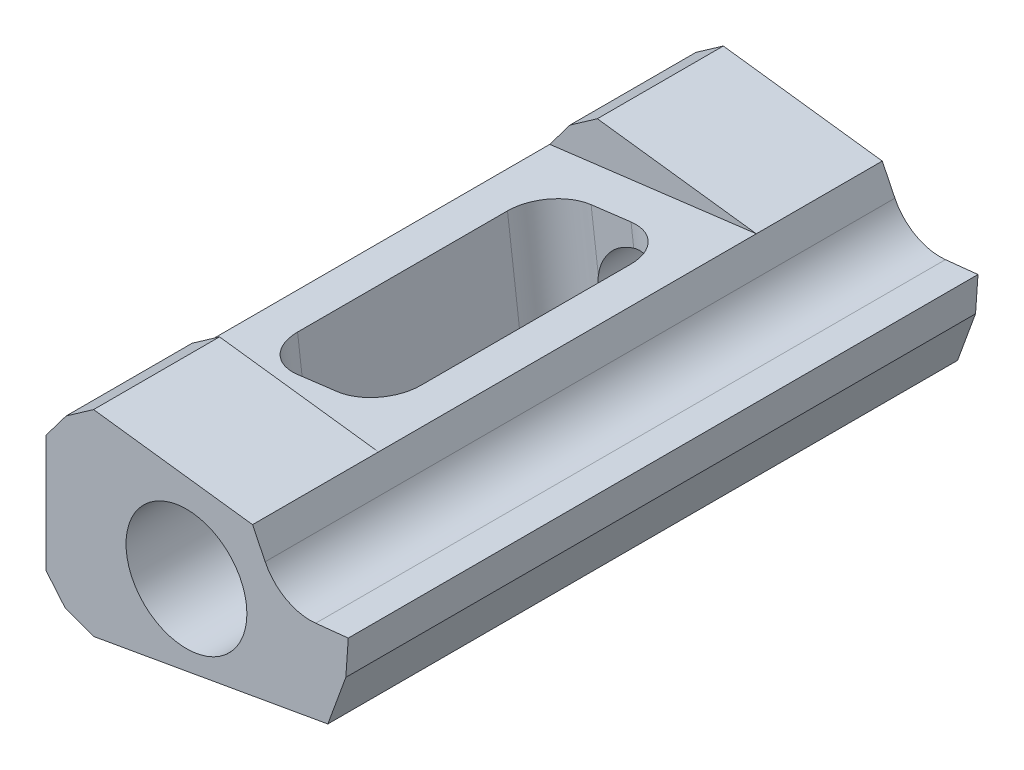
SolidWorks part; units mm, degrees
note: The reader was unsure of these and kept them because the rebuilt part matched: shared geometry of "Esboço7<3>", "Esboço7<4>".
material "AISI 4340 Aço, normalizado"
ref_plane "Plano frontal" through (0, 0, 0) normal (0, 0, 1) x (1, 0, 0)
ref_plane "Plano superior" through (0, 0, 0) normal (0, 1, 0) x (1, 0, 0)
ref_plane "Plano direito" through (0, 0, 0) normal (1, 0, 0) x (0, 0, -1)
other "Centro da massa"
sketch "Esboço1" plane through (0, 0, 0) normal (0, 0, 1) x (1, 0, 0)
  line L0 (0, 0) -> (23.1081, 0) construction
  line L1 (65, 0) -> (64.021, -14)
  line L2 (0, 0) -> (0, 38.7297) construction
  line L39 (27, 20) -> (-36.1134, 28)
  line L40 (-36.1134, 28) -> (-47, 20.3667)
  line L41 (-47, 20.3667) -> (-55, 9.7466)
  line L42 (-55, 9.7466) -> (-55, -36.7754)
  line L43 (-55, -36.7754) -> (-47.3284, -45.918)
  line L44 (-47.3284, -45.918) -> (-36.1134, -50)
  line L45 (-36.1134, -50) -> (56.8866, -33.6016)
  line L47 (56.8866, -33.6016) -> (64.021, -14)
  line L49 (65, 0) -> (52.0712, -1.3589)
  line L50 (32.0133, 9.7466) -> (27, 20)
  arc A0 (52.0712, -1.3589) -> (32.0133, 9.7466) centre (49.9806, 18.5316) cw
  dimension "D2" = 20
  dimension "D1" = 6
  dimension "D3" = 65
  dimension "D4" = 4
  dimension "D5" = 20
  dimension "D6" = 14
  dimension "D7" = 10
  dimension "D8" = 50
  dimension "D9" = 140
  dimension "D10" = 150
  dimension "D11" = 93
  dimension "D12" = 55
  dimension "D13" = 28
  dimension "D14" = 20
  dimension "D15" = 47
  dimension "D16" = 13
  dimension "D17" = 27
extrude "Ressalto-extrusão1" add sketch "Esboço1" along normal blind 250 contours L40 L41 L42 L43 L44 L45 L47 L1 L49 A0 L50 L39
scale "Escala1" scale about centroid uniform scaling yes scale factor 1.5
sketch "Esboço4" plane through (0, 0, -62.5) normal (0, 0, -1) x (-1, 0, 0)
  line L3 (80.808, -49.321) -> (69.3006, -63.0349) construction
  line L4 (69.3006, -63.0349) -> (52.478, -69.1578) construction
  line L5 (52.478, -69.1578) -> (-87.022, -44.5602) construction
  line L8 (80.808, -49.321) -> (69.3006, -63.0349)
  line L9 (69.3006, -63.0349) -> (52.478, -69.1578)
  line L10 (52.478, -69.1578) -> (-87.022, -44.5602)
  line L11 (52.478, 47.8422) -> (-42.192, 35.8422)
  line L12 (-42.192, 35.8422) -> (-49.712, 20.462)
  line L13 (-79.7988, 3.8039) -> (-99.192, 5.8422)
  line L14 (-99.192, 5.8422) -> (-97.7236, -15.1578)
  line L15 (-97.7236, -15.1578) -> (-87.022, -44.5602)
  line L16 (-87.022, -44.5602) -> (52.478, -69.1578)
  line L17 (52.478, -69.1578) -> (69.3006, -63.0349)
  line L18 (69.3006, -63.0349) -> (80.808, -49.321)
  line L19 (80.808, -49.321) -> (80.808, 20.462)
  line L20 (80.808, 20.462) -> (68.808, 36.3922)
  line L21 (68.808, 36.3922) -> (52.478, 47.8422)
  line L22 (52.478, 47.8422) -> (-42.192, 35.8422)
  line L31 (80.808, 20.462) -> (68.808, 36.3922)
  line L32 (68.808, 36.3922) -> (52.478, 47.8422)
  line L37 (-42.192, 35.8422) -> (80.808, 20.462)
  line L39 (-49.712, 20.462) -> (-42.192, 35.8422) construction
  line L40 (-87.022, -44.5602) -> (80.808, -49.321)
  arc A1 (-79.7988, 3.8039) -> (-49.712, 20.462) centre (-76.663, 33.6395) ccw
  point P3 (90.9399, 21.4695)
  dimension "D1" = 0
extrude "Corte-extrusão1" cut sketch "Esboço4" against normal offset from surface (225 mm away) 75 from offset 75 offset against normal yes
sketch "Esboço6" plane through (-3.7632, 30.0958, 0) normal (-0.1241, 0.9923, 0) x (0.9923, 0.1241, 0)
  line L0 (-46.1365, -12.5) -> (46.3131, -12.5) construction
  line L1 (-27.6447, -37.5) -> (-3.6869, -37.5)
  line L2 (-52.6447, -62.5) -> (-52.6447, -187.5)
  line L3 (-27.6447, -212.5) -> (-3.6869, -212.5)
  line L4 (21.3131, -62.5) -> (21.3131, -187.5)
  line L5 (46.3131, -237.5) -> (-46.1365, -237.5) construction
  line L6 (-77.6447, -237.5) -> (-77.6447, -12.5) construction
  line L7 (46.3131, -237.5) -> (46.3131, -12.5) construction
  arc A0 (-3.6869, -212.5) -> (21.3131, -187.5) centre (-3.6869, -187.5) ccw
  arc A1 (-52.6447, -187.5) -> (-27.6447, -212.5) centre (-27.6447, -187.5) ccw
  arc A2 (-3.6869, -37.5) -> (21.3131, -62.5) centre (-3.6869, -62.5) cw
  arc A3 (-27.6447, -37.5) -> (-52.6447, -62.5) centre (-27.6447, -62.5) ccw
  dimension "D5" = 25
  dimension "D1" = 25
  dimension "D2" = 25
  dimension "D3" = 25
  dimension "D4" = 25
extrude "Corte-extrusão3" cut sketch "Esboço6" against normal through all and the other way through all
sketch "Esboço7" plane through (0, 0, 312.5) normal (0, 0, 1) x (1, 0, 0)
  circle A0 centre (2.826, -11.7977) radius 36
  circle A1 centre (2.826, -11.7977) radius 30
  point P2 (-7.1795, -10.6794)
  point P3 (0, 0)
  point P4 (6.688, -14.5469)
  point P5 (2.826, -11.7977)
  dimension "D1" = 72
  dimension "D2" = 60
extrude "Corte-extrusão4" cut sketch "Esboço7" against normal blind 69 contours A0
extrude "Corte-extrusão5" cut sketch "Esboço7<3>" against normal through all contours A1
sketch "Esboço7<3>" plane through (0, 0, 312.5) normal (0, 0, 1) x (1, 0, 0) same geometry as "Esboço7"
extrude "Corte-extrusão6" cut sketch "Esboço7<4>" along normal blind 69 from surface at -375 starting at face at (32.826, -11.7977, -62.5)
sketch "Esboço7<4>" plane through (0, 0, 312.5) normal (0, 0, 1) x (1, 0, 0) same geometry as "Esboço7"
sketch "Esboço8" [suppressed] plane through (0, 0, 312.5) normal (0, 0, 1) x (1, 0, 0)
  circle A0 centre (0.7817, -11.1101) radius 101.6479
  circle A1 centre (0.7817, -11.1101) radius 36 construction
sketch "Esboço10" plane through (0, 0, 312.5) normal (0, 0, 1) x (1, 0, 0)
  line L11 (42.192, 35.8422) -> (-52.478, 47.8422)
  line L12 (-52.478, 47.8422) -> (-68.808, 36.3922)
  line L13 (-68.808, 36.3922) -> (-80.808, 20.462)
  line L14 (-80.808, 20.462) -> (-80.808, -49.321)
  line L15 (-80.808, -49.321) -> (-69.3006, -63.0349)
  line L16 (-69.3006, -63.0349) -> (-52.478, -69.1578)
  line L17 (-52.478, -69.1578) -> (87.022, -44.5602)
  line L18 (87.022, -44.5602) -> (97.7236, -15.1578)
  line L19 (97.7236, -15.1578) -> (99.192, 5.8422)
  line L20 (99.192, 5.8422) -> (79.7988, 3.8039)
  line L21 (49.712, 20.462) -> (42.192, 35.8422)
  line L22 (42.192, 35.8422) -> (-52.478, 47.8422)
  line L23 (-52.478, 47.8422) -> (-68.808, 36.3922)
  line L24 (-68.808, 36.3922) -> (-80.808, 20.462)
  line L25 (-80.808, 20.462) -> (-80.808, -49.321)
  line L26 (-80.808, -49.321) -> (-69.3006, -63.0349)
  line L27 (-69.3006, -63.0349) -> (-52.478, -69.1578)
  line L28 (-52.478, -69.1578) -> (87.022, -44.5602)
  line L29 (87.022, -44.5602) -> (97.7236, -15.1578)
  line L30 (97.7236, -15.1578) -> (99.192, 5.8422)
  line L31 (99.192, 5.8422) -> (79.7988, 3.8039)
  line L32 (49.712, 20.462) -> (42.192, 35.8422)
  circle A0 centre (2.826, -11.7977) radius 36 construction
  arc A1 (49.712, 20.462) -> (79.7988, 3.8039) centre (76.663, 33.6395) ccw
  arc A2 (49.712, 20.462) -> (79.7988, 3.8039) centre (76.663, 33.6395) ccw
  circle A3 centre (2.826, -11.7977) radius 36
  dimension "D1" = 0
